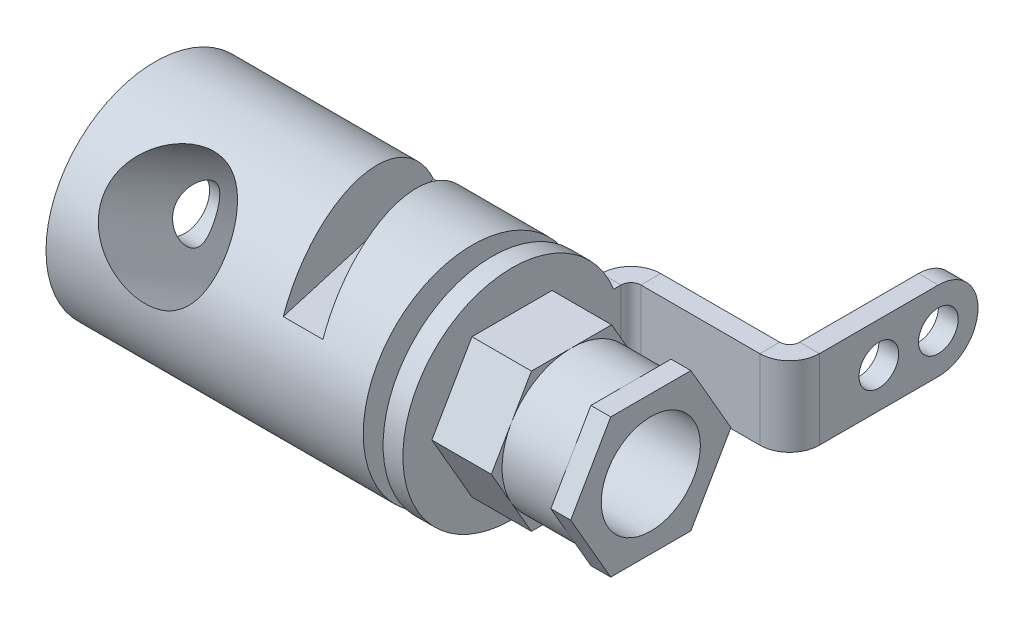
SolidWorks part; units mm, degrees
material "3003 Alloy"
ref_plane "Front" through (0, 0, 0) normal (0, 0, 1) x (1, 0, 0)
ref_plane "Top" through (0, 0, 0) normal (0, 1, 0) x (1, 0, 0)
ref_plane "Right" through (0, 0, 0) normal (1, 0, 0) x (0, 0, -1)
sketch "Sketch1" plane through (0, 0, 0) normal (1, 0, 0) x (0, 0, -1)
  circle A0 centre (0, 0) radius 5.5
  dimension "D1" = 11
extrude "Boss-Extrude1" add sketch "Sketch1" along normal blind 16 contours A0
sketch "Sketch2" plane through (16, 0, 0) normal (1, 0, 0) x (0, 0, -1)
  circle A0 centre (0, 0) radius 3.5
  circle A1 centre (0, 0) radius 5.5 construction
  dimension "D1" = 2
extrude "Boss-Extrude2" add sketch "Sketch2" along normal blind 1
sketch "Sketch3" plane through (17, 0, 0) normal (1, 0, 0) x (0, 0, -1)
  circle A0 centre (0, 0) radius 5.5
extrude "Boss-Extrude3" add sketch "Sketch3" along normal blind 1
ref_plane "Plane1" through (0, 0, 0) normal (0, 1, 0) x (1, 0, 0)
sketch "Sketch4" plane through (0, 0, 0) normal (0, 1, 0) x (1, 0, 0)
  line L2 (18.5, 6.5) -> (24.5, 6.5)
  line L3 (25.5, 7.5) -> (25.5, 15.5)
  line L4 (17.5, 5.5) -> (17.5, 4.3315)
  arc A0 (24.5, 6.5) -> (25.5, 7.5) centre (24.5, 7.5) ccw
  arc A1 (17.5, 5.5) -> (18.5, 6.5) centre (18.5, 5.5) cw
  point P3 (17.5, 6.5)
  point P8 (25.5, 6.5)
  dimension "D4" = 1
  dimension "D1" = 1
  dimension "D2" = 8
  dimension "D3" = 9
ref_plane "Plane2" through (0, 0, -15.5) normal (0, 0, 1) x (1, 0, 0)
sketch "Sketch5" plane through (0, 0, -15.5) normal (0, 0, 1) x (1, 0, 0)
  line L1 (25, -2) -> (26, -2)
  line L2 (25, -2) -> (25, 2)
  line L3 (25, 2) -> (26, 2)
  line L4 (26, -2) -> (26, 2)
  line L5 (25, -2) -> (26, 2) construction
  line L6 (25, 2) -> (26, -2) construction
  point P0 (25.5, 0)
  dimension "D1" = 1
  dimension "D2" = 4
sweep "Sweep1" add profiles "Sketch5" path "Sketch4"
fillet "Fillet1" radius 2 2 edges at (25.5, -2, -15.5) (25.5, 2, -15.5)
sketch "Sketch6" plane through (0, 0, -15.5) normal (0, 0, 1) x (1, 0, 0)
sketch "Sketch7" plane through (18, 0, 0) normal (1, 0, 0) x (0, 0, -1)
  line L1 (-2.0207, -3.5) -> (2.0207, -3.5)
  line L2 (2.0207, -3.5) -> (4.0415, 0)
  line L3 (4.0415, 0) -> (2.0207, 3.5)
  line L4 (2.0207, 3.5) -> (-2.0207, 3.5)
  line L5 (-2.0207, 3.5) -> (-4.0415, 0)
  line L6 (-4.0415, 0) -> (-2.0207, -3.5)
  circle A0 centre (0, 0) radius 3.5 construction
extrude "Boss-Extrude4" add sketch "Sketch7" along normal blind 3
sketch "Sketch8" plane through (21, 0, 0) normal (1, 0, 0) x (0, 0, -1)
  circle A0 centre (0, 0) radius 3.5
extrude "Boss-Extrude5" add sketch "Sketch8" along normal blind 3
sketch "Sketch9" plane through (24, 0, 0) normal (1, 0, 0) x (0, 0, -1)
  line L1 (-2.0207, -3.5) -> (2.0207, -3.5)
  line L2 (2.0207, -3.5) -> (4.0415, 0)
  line L3 (4.0415, 0) -> (2.0207, 3.5)
  line L4 (2.0207, 3.5) -> (-2.0207, 3.5)
  line L5 (-2.0207, 3.5) -> (-4.0415, 0)
  line L6 (-4.0415, 0) -> (-2.0207, -3.5)
  circle A0 centre (0, 0) radius 3.5 construction
extrude "Boss-Extrude7" add sketch "Sketch9" along normal blind 1 contours L4 L5 L6 L1 L2 L3
sketch "Sketch17" plane through (25, 0, 0) normal (1, 0, 0) x (0, 0, -1)
  circle A0 centre (0, 0) radius 2.5
extrude "Cut-Extrude7" cut sketch "Sketch17" against normal blind 6
sketch "Sketch18" plane through (19, 0, 0) normal (1, 0, 0) x (0, 0, -1)
  circle A0 centre (0, 0) radius 1.25
  dimension "D1" = 2.5
extrude "Cut-Extrude8" cut sketch "Sketch18" against normal through all
cosmetic thread "Cosmetic Thread1" parameters "D2"=3
sketch "Sketch19" plane through (0, 0, 0) normal (-1, 0, 0) x (0, 0, 1)
  circle A0 centre (0, 0) radius 4.5
extrude "Cut-Extrude9" cut sketch "Sketch19" against normal blind 1.5
ref_plane "Plane5" through (0, -2.75, -4.7631) normal (0, -0.5, -0.866) x (-1, 0, 0)
sketch "Sketch21" plane through (0, -2.75, -4.7631) normal (0, -0.5, -0.866) x (-1, 0, 0)
  circle A0 centre (-5.0018, 0.406) radius 3
extrude "Cut-Extrude10" cut sketch "Sketch21" against normal through all
ref_plane "Plane6" through (0, 5.5, 0) normal (0, 1, 0) x (1, 0, 0)
sketch "Sketch23" plane through (0, 5.5, 0) normal (0, 1, 0) x (1, 0, 0)
  line L0 (16, 5.5) -> (11, 5.5) construction
  line L1 (16, 5.5) -> (6.8742, 5.5) construction
  line L2 (16, -5.5) -> (13.5, -5.5) construction
  line L3 (16, -5.5) -> (16, 5.5) construction
  line L4 (11, 5.5) -> (13.5, -5.5)
  line L5 (13.5, -5.5) -> (11.5, -5.5)
  line L6 (11.5, -5.5) -> (9, 5.5)
  line L7 (9, 5.5) -> (11, 5.5)
  dimension "D1" = 2.5
  dimension "D2" = 2
extrude "Cut-Extrude12" cut sketch "Sketch23" against normal blind 3
sketch "Sketch24" plane through (25, 0, 0) normal (-1, 0, 0) x (0, 0, 1)
  circle A0 centre (-13.5, 0) radius 1
  circle A1 centre (-10.5, 0) radius 1
  dimension "D1" = 2
  dimension "D2" = 2
  dimension "D3" = 2
  dimension "D4" = 3
extrude "Cut-Extrude13" cut sketch "Sketch24" against normal blind 3
